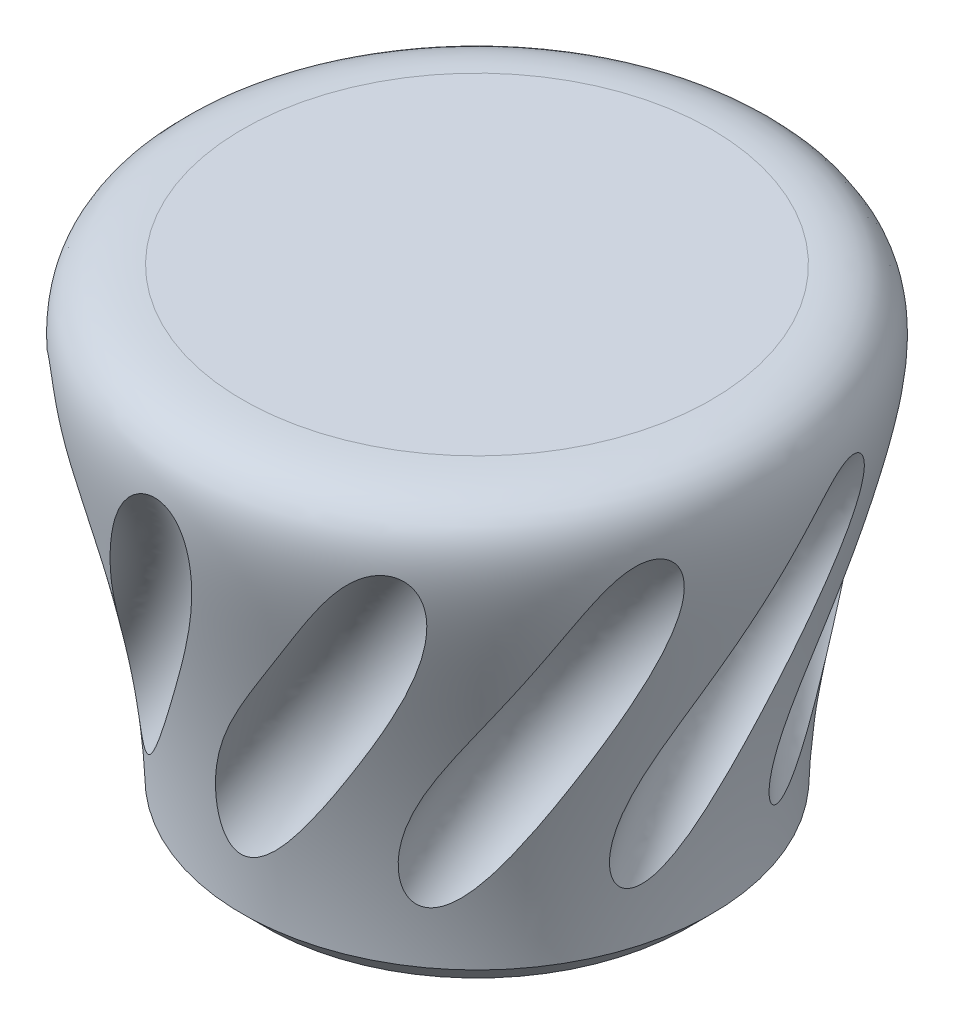
SolidWorks part; units mm, degrees
ref_plane "Front Plane" through (0, 0, 0) normal (0, 0, 1) x (1, 0, 0)
ref_plane "Top Plane" through (0, 0, 0) normal (0, 1, 0) x (1, 0, 0)
ref_plane "Right Plane" through (0, 0, 0) normal (1, 0, 0) x (0, 0, -1)
sketch "Sketch1" plane through (0, 0, 0) normal (0, 0, 1) x (1, 0, 0)
  line L0 (0, 0) -> (10, 0)
  line L1 (0, 20) -> (10, 20)
  line L2 (0, 0) -> (0, 20)
  line L3 (16.6481, 20) -> (9.3411, 20) construction
  line L4 (10, -9.4456) -> (10, 9.4536) construction
  line L5 (0, 20) -> (0, 0) construction
  line L6 (13, 20) -> (13, 0) construction
  spline S0 degree 3 poles (10, 20) (16.7136, 20) (10, 11.812) (10, 0) knots 0 0 0 0 1 1 1 1
  dimension "D1" = 10
  dimension "D2" = 20
  dimension "D3" = 3
revolve "Revolve1" add sketch "Sketch1" angle 360 about L2
chamfer "Chamfer1" distance 1 angle 45 1 edges at (0, 0, -10)
sketch "Sketch2" plane through (0, 0, 0) normal (0, -1, 0) x (1, 0, 0)
  circle A0 centre (0, 0) radius 3.08
  dimension "D1" = 6.16
extrude "Cut-Extrude1" cut sketch "Sketch2" against normal blind 13.4
sketch "Sketch3" plane through (0, 20, 0) normal (0, 1, 0) x (1, 0, 0)
  line L0 (-8, -6) -> (8, -6) construction
  line L1 (0, 0) -> (0, -6) construction
  circle A0 centre (0, 0) radius 10 construction
  dimension "D1" = 6
sketch "Sketch4" plane through (0, 0, 0) normal (0, -1, 0) x (1, 0, 0)
  line L0 (-6.7082, -6) -> (6.7082, -6) construction
  line L1 (0, 0) -> (0, -6) construction
  circle A0 centre (0, 0) radius 9 construction
  dimension "D1" = 6
ref_plane "Plane1" through (0, 2.6471, -4.4118) normal (0, -0.5145, 0.8575) x (1, 0, 0)
sketch "Sketch5" plane through (0, 2.6471, -4.4118) normal (0, -0.5145, 0.8575) x (1, 0, 0)
  circle A0 centre (-36.2637, 4.5117) radius 25
  dimension "D1" = 50
ref_plane "Plane2" through (0, -2.6471, -1.5882) normal (0, -0.8575, -0.5145) x (1, 0, 0)
sketch "Sketch6" plane through (0, -2.6471, -1.5882) normal (0, -0.8575, -0.5145) x (1, 0, 0)
  circle A0 centre (-12.4465, -5.145) radius 2
  dimension "D1" = 4
sweep "Cut-Sweep1" cut profiles "Sketch6" path "Sketch5"
pattern_circular "CirPattern1" count 10 over 360 of "Cut-Sweep1"
chamfer "Chamfer2" distance 1 angle 45 1 edges at (0, 0, -3.08)
ref_plane "Plane3" through (0, 30, 0) normal (0, 1, 0) x (1, 0, 0)
sketch "Sketch7" plane through (0, 30, 0) normal (0, 1, 0) x (1, 0, 0)
  line L0 (-8.6603, -5) -> (8.6603, -5) construction
  circle A0 centre (0, 0) radius 10 construction
  dimension "D1" = 5
sketch "Sketch8" plane through (0, 13.4, 0) normal (0, -1, 0) x (1, 0, 0)
  line L0 (-1.9, 2.4241) -> (1.9, 2.4241)
  circle A0 centre (0, 0) radius 3.08 construction
  arc A1 (1.9, 2.4241) -> (-1.9, 2.4241) centre (0, 0) ccw
  dimension "D1" = 3.8
extrude "Boss-Extrude1" add sketch "Sketch8" along normal up to surface (12.4 mm away) up to face at (0, 0, -4.08)
equation "\"diameter\"= 26mm"
equation "\"D1@Sketch1\"=.5*\"diameter\"-3"
equation "\"height\"= 20mm"
equation "\"D2@Sketch1\"=\"height\""
equation "\"shaft_dia\"= 6.16"
equation "\"D1@Sketch2\"=\"shaft_dia\""
equation "\"shaft_length\"= 13.4mm"
equation "\"D1@Cut-Extrude1\"=\"shaft_length\""
equation "\"A\"= 6mm"
equation "\"D1@Sketch3\"=\"A\""
equation "\"D1@Sketch4\"=\"A\""
